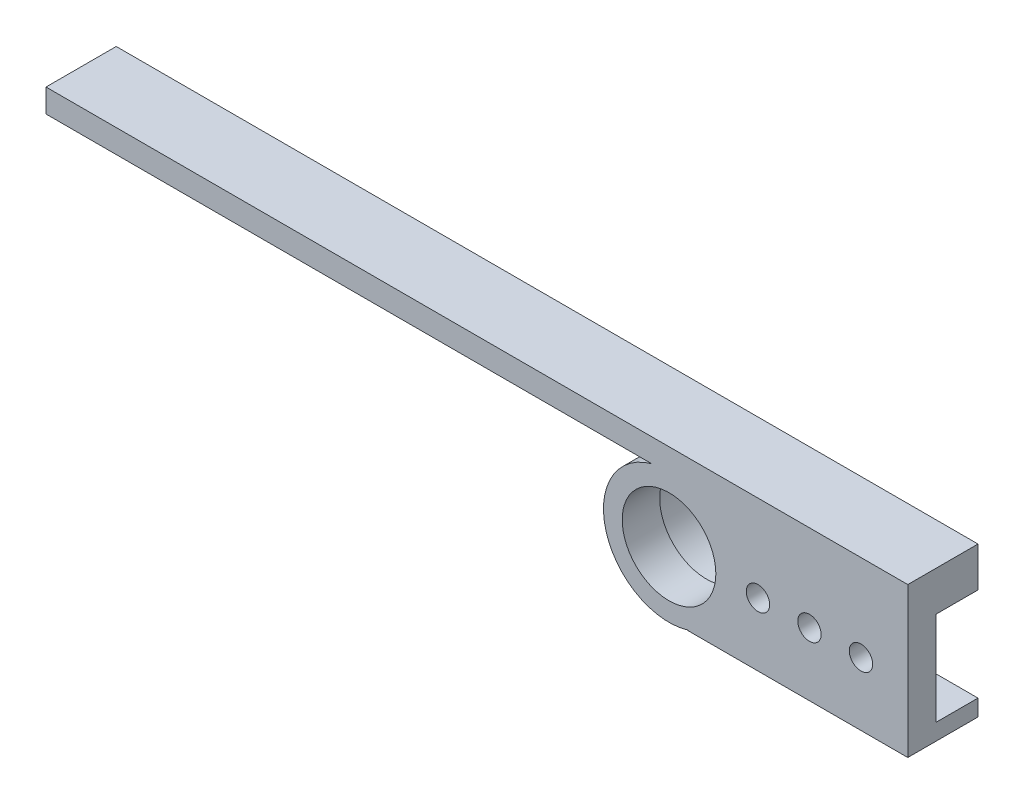
SolidWorks part; units mm, degrees
ref_plane "前视基准面" through (0, 0, 0) normal (0, 0, 1) x (1, 0, 0)
ref_plane "上视基准面" through (0, 0, 0) normal (0, 1, 0) x (1, 0, 0)
ref_plane "右视基准面" through (0, 0, 0) normal (1, 0, 0) x (0, 0, -1)
sketch "草图1" plane through (0, 0, 0) normal (0, 0, 1) x (1, 0, 0)
  line L1 (20, -10) -> (-20, -10)
  line L2 (20, -10) -> (20, 10)
  line L3 (20, 10) -> (-20, 10)
  line L4 (-20, -10) -> (-20, 10)
  line L5 (20, -10) -> (-20, 10) construction
  line L6 (20, 10) -> (-20, -10) construction
  point P0 (0, 0)
  dimension "D1" = 40
  dimension "D2" = 20
extrude "凸台-拉伸1" add sketch "草图1" along normal blind 6
sketch "草图2" plane through (0, 0, 6) normal (0, 0, 1) x (1, 0, 0)
  line L0 (20, -10) -> (20, 10) construction
  circle A0 centre (10, 0) radius 2.5
  circle A1 centre (-1, 0) radius 2.5
  circle A2 centre (-12, 0) radius 2.5
  dimension "D1" = 10
  dimension "D2" = 5
  dimension "D3" = 3
extrude "切除-拉伸1" cut sketch "草图2" against normal through all
sketch "草图3" plane through (0, 0, 6) normal (0, 0, 1) x (1, 0, 0)
  line L0 (20, 13.5) -> (20, 10)
  line L1 (20, -13.5) -> (-26.894, -13.5)
  line L3 (20, 13.5) -> (-26.894, 13.5)
  line L4 (-20, 10) -> (-20, -10)
  line L5 (-20, -10) -> (20, -10)
  line L6 (20, -10) -> (20, 10)
  line L7 (20, 10) -> (-20, 10)
  line L8 (-20, 10) -> (-20, -10)
  line L9 (-20, -10) -> (20, -10)
  line L10 (20, -10) -> (20, 10)
  line L11 (20, 10) -> (-20, 10)
  line L12 (-26.894, -13.5) -> (-26.894, 13.5)
  line L13 (20, -10.0394) -> (-26.894, 13.5) construction
  line L14 (20, 10.0394) -> (-26.894, -13.5) construction
  line L15 (20, -10) -> (20, -13.5)
  circle A0 centre (-31, 0) radius 11
  circle A1 centre (-31, 0) radius 14
  point P2 (0, 0)
  line M10 (-20, 10) -> (-20, -10)
  line M11 (-20, -10) -> (20, -10)
  line M13 (20, 10) -> (-20, 10)
  dimension "D3" = 22
  dimension "D4" = 28
  dimension "D2" = 3.5
  dimension "D1" = 0
extrude "凸台-拉伸2" add sketch "草图3" against normal blind 15 contours L3 A1 L1 L12 A0 | A1 L1 L15 M11 M10 | L1 A1 L8 A0 L12 | L8 A1 L3 L12 A0 | L8 A1 | A1 L0 L3 M10 M13 region at (-1.9449, 11.7771, 6) region at (-1.9449, -11.7771, 6) region at (-23.0173, 9.0328, 6) region at (-27.2274, 11.7946, 6) region at (-18.7882, 0, 6) region at (-23.0173, -9.0328, 6)
sketch "草图5" plane through (0, 0, 6) normal (0, 0, 1) x (1, 0, 0)
  circle A0 centre (-31, 0) radius 10
  circle A1 centre (-31, 0) radius 11 construction
  circle A2 centre (-31, 0) radius 11
  dimension "D1" = 20
extrude "凸台-拉伸3" add sketch "草图5" against normal blind 8
sketch "草图6" plane through (0, 0, 6) normal (0, 0, 1) x (1, 0, 0)
  circle A0 centre (-31, 0) radius 8.5
  circle A1 centre (-31, 0) radius 10 construction
  circle A2 centre (-31, 0) radius 10
  dimension "D1" = 17
sketch "草图7" plane through (0, 13.5, 0) normal (0, 1, 0) x (1, 0, 0)
  circle A0 centre (-16.8213, 3.0525) radius 3.3366
sketch "草图8" plane through (20, 0, 0) normal (1, 0, 0) x (0, 0, -1)
  line L1 (-6, 13.5) -> (9, 13.5)
  line L2 (-6, 13.5) -> (-6, 18.5)
  line L3 (-6, 18.5) -> (9, 18.5)
  line L4 (9, 13.5) -> (9, 18.5)
  dimension "D1" = 5
extrude "凸台-拉伸4" add sketch "草图8" against normal blind 200
sketch "草图9" plane through (0, 0, 6) normal (0, 0, 1) x (1, 0, 0)
  line L1 (-29.5663, 15.6648) -> (-25.1627, 15.6648)
  line L2 (-29.5663, 15.6648) -> (-29.5663, 11.9284)
  line L3 (-29.5663, 11.9284) -> (-25.1627, 11.9284)
  line L4 (-25.1627, 15.6648) -> (-25.1627, 11.9284)
extrude "凸台-拉伸5" add sketch "草图9" against normal through all
sketch "草图11" plane through (0, 18.5, 0) normal (0, 1, 0) x (1, 0, 0)
  line L0 (-118.4338, -6) -> (-118.4338, 9)
  line L1 (-180, -6) -> (20, -6) construction
  line L2 (-118.4338, 246.7017) -> (-118.4338, -123.2983) construction
  line L3 (-180, 9) -> (20, 9) construction
sketch "草图13" plane through (0, 18.5, 0) normal (0, 1, 0) x (1, 0, 0)
  line L1 (-118.4338, -6) -> (-183.1111, -6)
  line L2 (-118.4338, -6) -> (-118.4338, 12.5245)
  line L3 (-118.4338, 12.5245) -> (-183.1111, 12.5245)
  line L4 (-183.1111, -6) -> (-183.1111, 12.5245)
extrude "切除-拉伸2" cut sketch "草图13" against normal through all
sketch "草图14" plane through (0, 18.5, 0) normal (0, 1, 0) x (1, 0, 0)
  line L0 (-164.0842, 11.0465) -> (-164.0842, -39.4434)
  line L1 (-164.0842, 248.4982) -> (-164.0842, -121.5018) construction
sketch "草图15" plane through (0, 18.5, 0) normal (0, 1, 0) x (1, 0, 0)
  line L0 (-164.0842, 11.0465) -> (-164.0842, -39.4434) construction
  line L1 (-118.4338, -6) -> (-164.0842, -6)
  line L2 (-118.4338, -6) -> (-118.4338, 9)
  line L3 (-118.4338, 9) -> (-164.0842, 9)
  line L4 (-164.0842, -6) -> (-164.0842, 9)
extrude "凸台-拉伸6" add sketch "草图15" against normal blind 5
